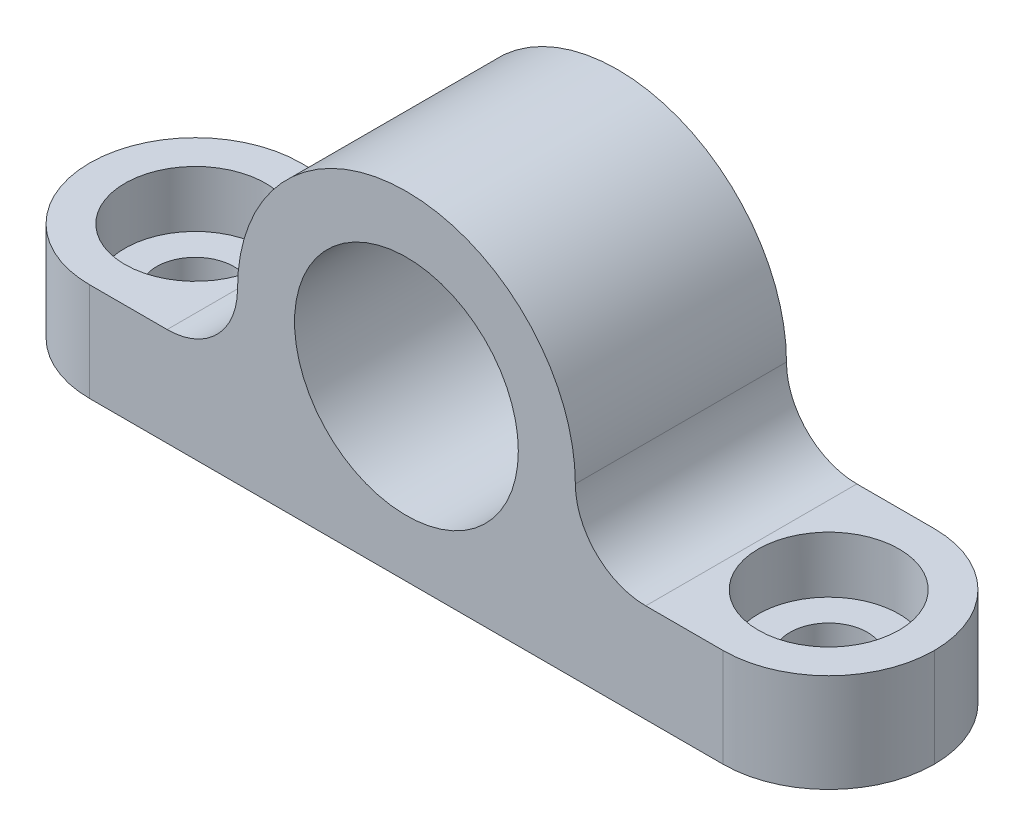
SolidWorks part; units mm, degrees
material "ABS"
ref_plane "Front Plane" through (0, 0, 0) normal (0, 0, 1) x (1, 0, 0)
ref_plane "Top Plane" through (0, 0, 0) normal (0, 1, 0) x (1, 0, 0)
ref_plane "Right Plane" through (0, 0, 0) normal (1, 0, 0) x (0, 0, -1)
sketch "Sketch1" plane through (0, 0, 0) normal (0, 1, 0) x (1, 0, 0)
  line L1 (-30, 7.5) -> (30, 7.5)
  line L2 (-30, 7.5) -> (-30, -7.5)
  line L3 (-30, -7.5) -> (30, -7.5)
  line L4 (30, 7.5) -> (30, -7.5)
  line L5 (-30, 7.5) -> (30, -7.5) construction
  line L6 (-30, -7.5) -> (30, 7.5) construction
  point P0 (0, 0)
  dimension "D1" = 15
  dimension "D2" = 60
extrude "Boss-Extrude1" add sketch "Sketch1" along normal blind 7
sketch "Sketch2" plane through (0, 7, 0) normal (0, 1, 0) x (1, 0, 0)
  line L0 (0, 0) -> (0, 16.1547) construction
  line L1 (30, 7.5) -> (-30, 7.5) construction
  line L2 (-30, 7.5) -> (-30, -7.5) construction
  circle A0 centre (-22.5, 0) radius 2.75
  circle A1 centre (22.5, 0) radius 2.75
  dimension "D3" = 5.5
  dimension "D1" = 7.5
  dimension "D2" = 7.5
extrude "Cut-Extrude1" cut sketch "Sketch2" against normal through all
sketch "Sketch3" plane through (0, 7, 0) normal (0, 1, 0) x (1, 0, 0)
  line L0 (0, 0) -> (0, 12.9854) construction
  circle A0 centre (-22.5, 0) radius 5
  circle A1 centre (22.5, 0) radius 5
  dimension "D1" = 10
extrude "Cut-Extrude2" cut sketch "Sketch3" against normal offset from surface (4 mm away) 3 up to face at (22.5, 0, -2.75)
sketch "Sketch4" plane through (0, 0, 7.5) normal (0, 0, 1) x (1, 0, 0)
  line L0 (-30, 7) -> (30, 7) construction
  line L1 (-12, 12) -> (12, 12) construction
  line L2 (-12, 12) -> (-12, 7) construction
  line L3 (-17, 7) -> (17, 7)
  line L4 (12, 12) -> (12, 7) construction
  line L5 (-12, 12) -> (12, 7) construction
  line L6 (-12, 7) -> (12, 12) construction
  line L7 (-30, 0) -> (30, 0) construction
  arc A0 (-12, 12) -> (12, 12) centre (0, 12) cw
  arc A1 (-12, 12) -> (-17, 7) centre (-17, 12) cw
  arc A2 (12, 12) -> (17, 7) centre (17, 12) ccw
  point P0 (0, 9.5)
  point P9 (0, 0)
  dimension "D2" = 12
  dimension "D1" = 12
extrude "Boss-Extrude2" add sketch "Sketch4" against normal up to surface (15 mm away) up to face at (0, 3.5, -7.5)
sketch "Sketch5" plane through (0, 0, 7.5) normal (0, 0, 1) x (1, 0, 0)
  circle A0 centre (0, 12) radius 7.95
  circle A2 centre (0, 12) radius 7.95 construction
  arc A3 (12, 12) -> (-12, 12) centre (0, 12) ccw construction
extrude "Cut-Extrude3" cut sketch "Sketch5" against normal through all
fillet "Fillet2" radius 7.5 4 edges at (30, 3.5, 7.5) (30, 3.5, -7.5) (-30, 3.5, -7.5) (-30, 3.5, 7.5)
equation "\"D2@Sketch2\" = \"D1@Sketch2\""
equation "\"D1@Sketch4\" = \"D2@Sketch4\""
